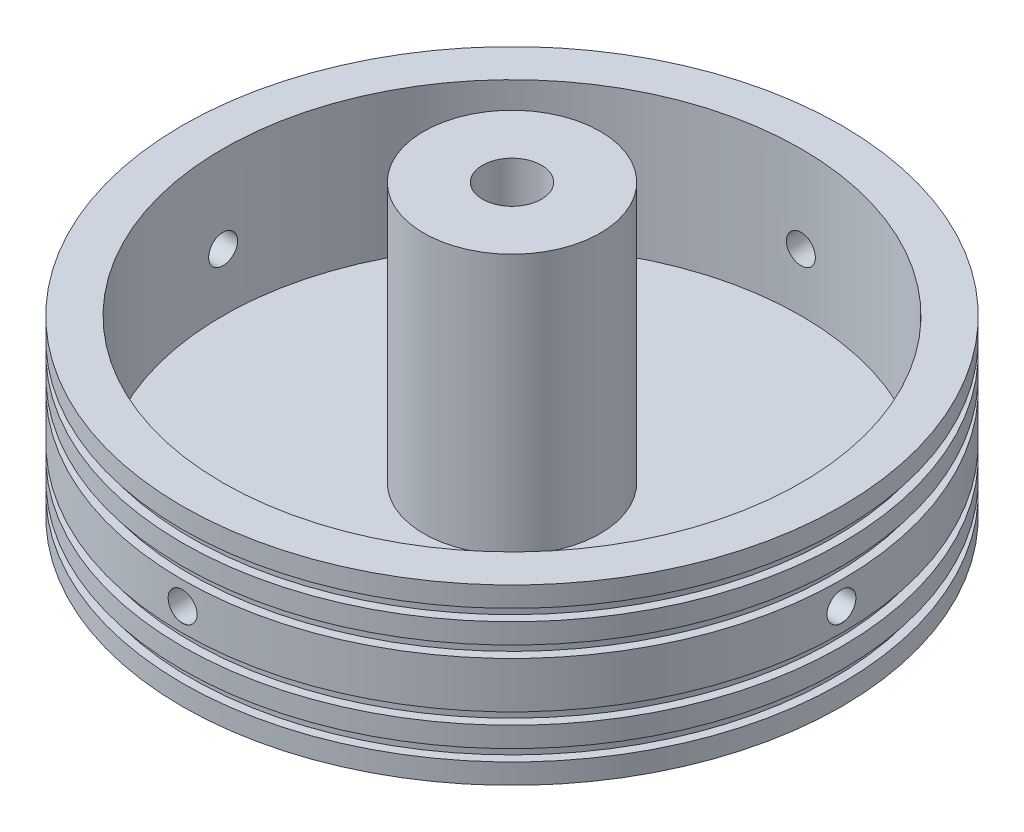
SolidWorks part; units mm, degrees
material "6061-T6 (SS)"
ref_plane "Front Plane" through (0, 0, 0) normal (0, 0, 1) x (1, 0, 0)
ref_plane "Top Plane" through (0, 0, 0) normal (0, 1, 0) x (1, 0, 0)
ref_plane "Right Plane" through (0, 0, 0) normal (1, 0, 0) x (0, 0, -1)
sketch "Sketch1" plane through (0, 0, 0) normal (0, 0, 1) x (1, 0, 0)
  line L0 (0, 0) -> (0, 50000) construction
  line L11 (0, 0) -> (0, 50)
  line L12 (0, 50) -> (15.25, 50)
  line L13 (15.25, 50) -> (15.25, 5)
  line L14 (15.25, 5) -> (50, 5)
  line L15 (50, 5) -> (50, 30)
  line L16 (50, 30) -> (57, 30)
  line L17 (57, 30) -> (57, 26.5)
  line L18 (55, 0) -> (-55, 0) construction
  line L19 (57, 0) -> (0, 0)
  line L21 (57, 26.5) -> (55.5, 26.5)
  line L23 (57, 24.5) -> (55.5, 24.5)
  line L24 (55.5, 26.5) -> (55.5, 24.5)
  line L25 (57, 21) -> (55.5, 21)
  line L27 (57, 19) -> (55.5, 19)
  line L28 (55.5, 21) -> (55.5, 19)
  line L29 (57, 11) -> (55.5, 11)
  line L31 (57, 9) -> (55.5, 9)
  line L32 (55.5, 11) -> (55.5, 9)
  line L33 (57, 5.5) -> (55.5, 5.5)
  line L35 (57, 3.5) -> (55.5, 3.5)
  line L36 (55.5, 5.5) -> (55.5, 3.5)
  line L37 (57, 24.5) -> (57, 21)
  line L39 (57, 19) -> (57, 11)
  line L41 (57, 9) -> (57, 5.5)
  line L42 (57, 3.5) -> (57, 0)
  dimension "D1" = 30.5
  dimension "D2" = 50
  dimension "D3" = 30
  dimension "D4" = 5
  dimension "D5" = 114
  dimension "D6" = 100
  dimension "D7" = 8
  dimension "D8" = 2
  dimension "D9" = 1.5
revolve "Revolve1" add sketch "Sketch1" angle 360 about L0
hole_wizard "M5 Tapped Hole1" positions "3DSketch1" profile "Sketch2" tap size "M5" standard "ISO" end condition up to next
sketch3d "3DSketch1"
  point P16 (0, 15, 57)
  point P19 (1.7576, 15.02, 56.9729)
  point P20 (0, 15.02, 57)
  point P21 (0, 14.6705, 57)
  dimension "D1" = 15
sketch "Sketch2" plane through (0, 15, 57) normal (1, 0, 0) x (0, -1, 0)
  line L0 (0, 0) -> (0, 7)
  line L1 (0, 7) -> (2.5, 7)
  line L2 (2.5, 7) -> (2.5, 0.025)
  line L3 (2.5, 0.025) -> (2.525, 0)
  line L5 (2.525, 0) -> (0, 0)
  line L6 (-2.5, 0.025) -> (-2.525, 0) construction
  line L11 (0, -6.35) -> (0, 107.95) construction
  dimension "Thread Major Dia." = 5
  dimension "Thru Tap Drill Depth" = 7
  dimension "Near C'Sink Dia." = 5.05
  dimension "Near C'Sink Angle" = 90
pattern_circular "CirPattern1" count 4 over 360 about axis through (0, 0, 0) along (0, -1, 0) of "M5 Tapped Hole1" reverse direction yes
hole_wizard "M12 Tapped Hole1" positions "Sketch3" profile "Sketch4" tap size "M12" standard "ISO" end condition up to next
sketch "Sketch3" plane through (0, 0, 0) normal (0, 1, 0) x (1, 0, 0)
  point P15 (0, 0)
  point P18 (0, 0)
  point P19 (0, 0)
  point P20 (0, 0)
  point P22 (0, 0)
sketch "Sketch4" plane through (0, 0, 0) normal (1, 0, 0) x (0, 0, -1)
  line L0 (0, 0) -> (0, 50)
  line L1 (0, 50) -> (5.1, 50)
  line L2 (5.1, 50) -> (5.1, 0)
  line L5 (5.1, 0) -> (0, 0)
  line L11 (0, -6.35) -> (0, 107.95) construction
  dimension "Thru Tap Drill Dia." = 10.2
  dimension "Thru Tap Drill Depth" = 50
cosmetic thread "Hole Thread10" parameters "D2"=12
equation "\"CanSat_Len\"= 400mm"
equation "\"CanSat_Dia\"= 150mm"
equation "\"BodyTube_ID\"= 114mm"
equation "\"BodyTube_OD\"= 120mm"
equation "\"PayLoadBay_ID\"= 164mm"
equation "\"PayLoadBay_OD\"= 170mm"
equation "\"ParachuteBay_Pitch\"= 300mm"
equation "\"ElectronicsTray_PitchDist\"= 50mm"
equation "\"ElectronicsTray_Height\"= 140mm"
equation "\"D5@Sketch1\"=\"BodyTube_ID\""
